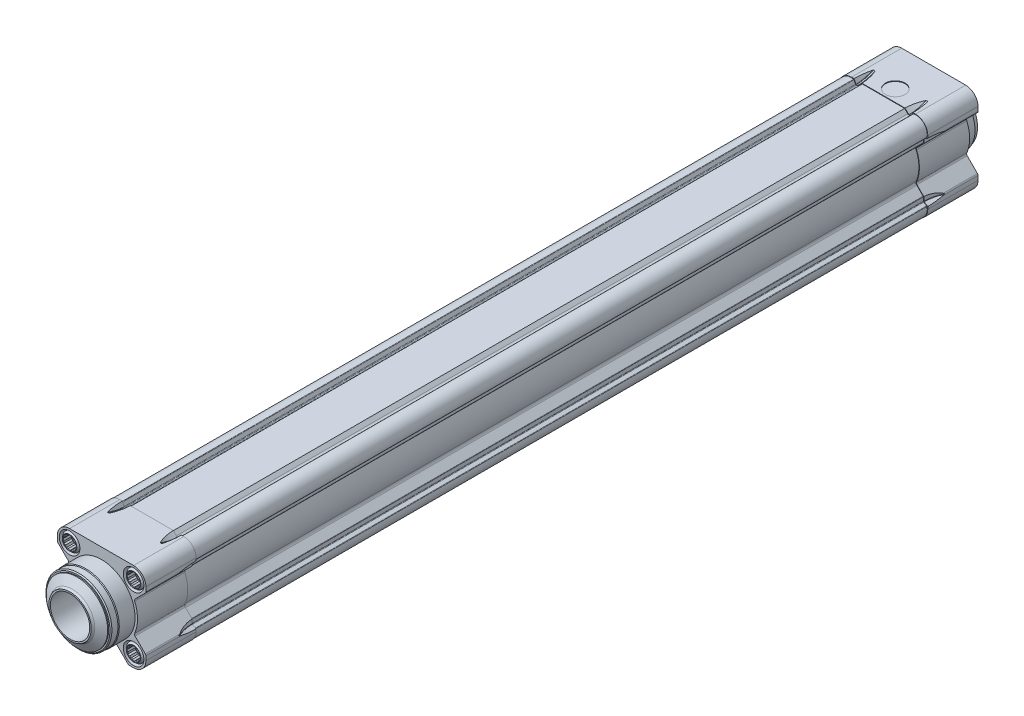
SolidWorks part; units mm, degrees
ref_plane "Front Plane" through (0, 0, 0) normal (0, 0, 1) x (1, 0, 0)
ref_plane "Top Plane" through (0, 0, 0) normal (0, 1, 0) x (1, 0, 0)
ref_plane "Right Plane" through (0, 0, 0) normal (1, 0, 0) x (0, 0, -1)
ref_plane "Plane4" through (0, 0, -25.5) normal (0, 0, 1) x (1, 0, 0)
sketch "Sketch1" plane through (0, 0, -25.5) normal (0, 0, 1) x (1, 0, 0)
  line L0 (-22.2071, 13.3683) -> (-17.0289, 8.1901)
  line L1 (-17.0289, -8.1901) -> (-22.2071, -13.3683)
  line L2 (-22.5, -14.0754) -> (-22.5, -16.25)
  line L3 (-16.25, -22.5) -> (-14.0754, -22.5)
  line L4 (-13.3683, -22.2071) -> (-8.1901, -17.0289)
  line L5 (8.1901, -17.0289) -> (13.3683, -22.2071)
  line L6 (14.0754, -22.5) -> (16.25, -22.5)
  line L7 (22.5, -16.25) -> (22.5, -14.0754)
  line L8 (22.2071, -13.3683) -> (17.0289, -8.1901)
  line L9 (17.0289, 8.1901) -> (22.2071, 13.3683)
  line L10 (22.5, 14.0754) -> (22.5, 16.25)
  line L11 (16.25, 22.5) -> (-16.25, 22.5)
  line L12 (-22.5, 16.25) -> (-22.5, 14.0754)
  arc A0 (-22.5, 14.0754) -> (-22.2071, 13.3683) centre (-21.5, 14.0754) ccw
  arc A1 (-17.0289, 8.1901) -> (-16.8147, 7.0943) centre (-17.736, 7.483) cw
  arc A2 (-16.8147, 7.0943) -> (-16.8147, -7.0943) centre (0, 0) ccw
  arc A3 (-16.8147, -7.0943) -> (-17.0289, -8.1901) centre (-17.736, -7.483) cw
  arc A4 (-22.2071, -13.3683) -> (-22.5, -14.0754) centre (-21.5, -14.0754) ccw
  arc A5 (-22.5, -16.25) -> (-16.25, -22.5) centre (-16.25, -16.25) ccw
  arc A6 (-14.0754, -22.5) -> (-13.3683, -22.2071) centre (-14.0754, -21.5) ccw
  arc A7 (-8.1901, -17.0289) -> (-7.0943, -16.8147) centre (-7.483, -17.736) cw
  arc A8 (-7.0943, -16.8147) -> (7.0943, -16.8147) centre (0, 0) ccw
  arc A9 (7.0943, -16.8147) -> (8.1901, -17.0289) centre (7.483, -17.736) cw
  arc A10 (13.3683, -22.2071) -> (14.0754, -22.5) centre (14.0754, -21.5) ccw
  arc A11 (16.25, -22.5) -> (22.5, -16.25) centre (16.25, -16.25) ccw
  arc A12 (22.5, -14.0754) -> (22.2071, -13.3683) centre (21.5, -14.0754) ccw
  arc A13 (17.0289, -8.1901) -> (16.8147, -7.0943) centre (17.736, -7.483) cw
  arc A14 (16.8147, -7.0943) -> (16.8147, 7.0943) centre (0, 0) ccw
  arc A15 (16.8147, 7.0943) -> (17.0289, 8.1901) centre (17.736, 7.483) cw
  arc A16 (22.2071, 13.3683) -> (22.5, 14.0754) centre (21.5, 14.0754) ccw
  arc A17 (22.5, 16.25) -> (16.25, 22.5) centre (16.25, 16.25) ccw
  arc A18 (-16.25, 22.5) -> (-22.5, 16.25) centre (-16.25, 16.25) ccw
extrude "Boss-Extrude1" add sketch "Sketch1" along normal blind 25.5
sketch "Sketch2" plane through (0, 0, -25.5) normal (0, 0, 1) x (1, 0, 0)
  line L0 (-15, 28.125) -> (-15, 22.5)
  line L1 (-15, 22.5) -> (-13.903, 20.6)
  line L2 (-13.7298, 20.5) -> (-13.0281, 20.5)
  line L3 (-12.8867, 20.5586) -> (-10.9453, 22.5)
  line L4 (-10.9453, 22.5) -> (10.9453, 22.5)
  line L5 (10.9453, 22.5) -> (12.8867, 20.5586)
  line L6 (13.0281, 20.5) -> (13.7298, 20.5)
  line L7 (13.903, 20.6) -> (15, 22.5)
  line L8 (15, 22.5) -> (15, 28.125)
  line L9 (15, 28.125) -> (-15, 28.125)
  line L10 (-50, 40.5) -> (50, 40.5) construction
  arc A0 (-13.903, 20.6) -> (-13.7298, 20.5) centre (-13.7298, 20.7) ccw
  arc A1 (-13.0281, 20.5) -> (-12.8867, 20.5586) centre (-13.0281, 20.7) ccw
  arc A2 (12.8867, 20.5586) -> (13.0281, 20.5) centre (13.0281, 20.7) ccw
  arc A3 (13.7298, 20.5) -> (13.903, 20.6) centre (13.7298, 20.7) ccw
revolve "Cut-Revolve1" cut sketch "Sketch2" angle 360 about L10 reverse direction yes
sketch "Sketch3" plane through (0, 0, -25.5) normal (0, 0, 1) x (1, 0, 0)
  line L0 (-15, -28.125) -> (15, -28.125)
  line L1 (15, -28.125) -> (15, -22.5)
  line L2 (15, -22.5) -> (13.903, -20.6)
  line L3 (13.7298, -20.5) -> (5.5958, -20.5)
  line L4 (-5.5958, -20.5) -> (-13.7298, -20.5)
  line L5 (-13.903, -20.6) -> (-15, -22.5)
  line L6 (-15, -22.5) -> (-15, -28.125)
  line L7 (50, -40.5) -> (-50, -40.5) construction
  arc A0 (13.903, -20.6) -> (13.7298, -20.5) centre (13.7298, -20.7) ccw
  arc A1 (5.5958, -20.5) -> (-5.5958, -20.5) centre (0, 0) cw
  arc A2 (-13.7298, -20.5) -> (-13.903, -20.6) centre (-13.7298, -20.7) ccw
revolve "Cut-Revolve2" cut sketch "Sketch3" angle 360 about L7 reverse direction yes
sketch "Sketch4" plane through (0, 0, -25.5) normal (0, 0, 1) x (1, 0, 0)
  line L0 (20.5, -5.5958) -> (20.5, -13.7298)
  line L1 (20.6, -13.903) -> (22.5, -15)
  line L2 (22.5, -15) -> (28.125, -15)
  line L3 (28.125, -15) -> (28.125, 15)
  line L4 (28.125, 15) -> (22.5, 15)
  line L5 (22.5, 15) -> (20.6, 13.903)
  line L6 (20.5, 13.7298) -> (20.5, 5.5958)
  line L7 (40.5, 50) -> (40.5, -50) construction
  arc A0 (20.5, -13.7298) -> (20.6, -13.903) centre (20.7, -13.7298) ccw
  arc A1 (20.6, 13.903) -> (20.5, 13.7298) centre (20.7, 13.7298) ccw
  arc A2 (20.5, 5.5958) -> (20.5, -5.5958) centre (0, 0) cw
revolve "Cut-Revolve3" cut sketch "Sketch4" angle 360 about L7 reverse direction yes
sketch "Sketch5" plane through (0, 0, -25.5) normal (0, 0, 1) x (1, 0, 0)
  line L0 (-28.125, -15) -> (-22.5, -15)
  line L1 (-22.5, -15) -> (-20.6, -13.903)
  line L2 (-20.5, -13.7298) -> (-20.5, -5.5958)
  line L3 (-20.5, 5.5958) -> (-20.5, 13.7298)
  line L4 (-20.6, 13.903) -> (-22.5, 15)
  line L5 (-22.5, 15) -> (-28.125, 15)
  line L6 (-28.125, 15) -> (-28.125, -15)
  line L7 (-40.5, -50) -> (-40.5, 50) construction
  arc A0 (-20.6, -13.903) -> (-20.5, -13.7298) centre (-20.7, -13.7298) ccw
  arc A1 (-20.5, -5.5958) -> (-20.5, 5.5958) centre (0, 0) cw
  arc A2 (-20.5, 13.7298) -> (-20.6, 13.903) centre (-20.7, 13.7298) ccw
revolve "Cut-Revolve4" cut sketch "Sketch5" angle 360 about L7 reverse direction yes
sketch "Sketch6" plane through (0, 0, 0) normal (1, 0, 0) x (0, 0, -1)
  line L0 (25.5, 0) -> (25.5, 5)
  line L1 (25.5, 5) -> (397, 5)
  line L2 (397, 5) -> (397, 0)
  line L3 (397, 0) -> (25.5, 0)
  line L4 (397, 0) -> (25.5, 0) construction
revolve "Revolve1" add sketch "Sketch6" angle 360 about L4 reverse direction yes
ref_plane "Plane5" through (0, 0, -397) normal (0, 0, 1) x (1, 0, 0)
sketch "Sketch7" plane through (0, 0, -397) normal (0, 0, 1) x (1, 0, 0)
  line L0 (-22.2071, 13.3683) -> (-17.0289, 8.1901)
  line L1 (-17.0289, -8.1901) -> (-22.2071, -13.3683)
  line L2 (-22.5, -14.0754) -> (-22.5, -16.25)
  line L3 (-16.25, -22.5) -> (-14.0754, -22.5)
  line L4 (-13.3683, -22.2071) -> (-8.1901, -17.0289)
  line L5 (8.1901, -17.0289) -> (13.3683, -22.2071)
  line L6 (14.0754, -22.5) -> (16.25, -22.5)
  line L7 (22.5, -16.25) -> (22.5, -14.0754)
  line L8 (22.2071, -13.3683) -> (17.0289, -8.1901)
  line L9 (17.0289, 8.1901) -> (22.2071, 13.3683)
  line L10 (22.5, 14.0754) -> (22.5, 16.25)
  line L11 (16.25, 22.5) -> (-16.25, 22.5)
  line L12 (-22.5, 16.25) -> (-22.5, 14.0754)
  arc A0 (-22.5, 14.0754) -> (-22.2071, 13.3683) centre (-21.5, 14.0754) ccw
  arc A1 (-17.0289, 8.1901) -> (-16.8147, 7.0943) centre (-17.736, 7.483) cw
  arc A2 (-16.8147, 7.0943) -> (-16.8147, -7.0943) centre (0, 0) ccw
  arc A3 (-16.8147, -7.0943) -> (-17.0289, -8.1901) centre (-17.736, -7.483) cw
  arc A4 (-22.2071, -13.3683) -> (-22.5, -14.0754) centre (-21.5, -14.0754) ccw
  arc A5 (-22.5, -16.25) -> (-16.25, -22.5) centre (-16.25, -16.25) ccw
  arc A6 (-14.0754, -22.5) -> (-13.3683, -22.2071) centre (-14.0754, -21.5) ccw
  arc A7 (-8.1901, -17.0289) -> (-7.0943, -16.8147) centre (-7.483, -17.736) cw
  arc A8 (-7.0943, -16.8147) -> (7.0943, -16.8147) centre (0, 0) ccw
  arc A9 (7.0943, -16.8147) -> (8.1901, -17.0289) centre (7.483, -17.736) cw
  arc A10 (13.3683, -22.2071) -> (14.0754, -22.5) centre (14.0754, -21.5) ccw
  arc A11 (16.25, -22.5) -> (22.5, -16.25) centre (16.25, -16.25) ccw
  arc A12 (22.5, -14.0754) -> (22.2071, -13.3683) centre (21.5, -14.0754) ccw
  arc A13 (17.0289, -8.1901) -> (16.8147, -7.0943) centre (17.736, -7.483) cw
  arc A14 (16.8147, -7.0943) -> (16.8147, 7.0943) centre (0, 0) ccw
  arc A15 (16.8147, 7.0943) -> (17.0289, 8.1901) centre (17.736, 7.483) cw
  arc A16 (22.2071, 13.3683) -> (22.5, 14.0754) centre (21.5, 14.0754) ccw
  arc A17 (22.5, 16.25) -> (16.25, 22.5) centre (16.25, 16.25) ccw
  arc A18 (-16.25, 22.5) -> (-22.5, 16.25) centre (-16.25, 16.25) ccw
extrude "Boss-Extrude2" add sketch "Sketch7" against normal blind 25.5
sketch "Sketch8" plane through (0, 0, -397) normal (0, 0, 1) x (1, 0, 0)
  line L0 (-15, 28.125) -> (-15, 22.5)
  line L1 (-15, 22.5) -> (-13.903, 20.6)
  line L2 (-13.7298, 20.5) -> (-13.0281, 20.5)
  line L3 (-12.8867, 20.5586) -> (-10.9453, 22.5)
  line L4 (-10.9453, 22.5) -> (10.9453, 22.5)
  line L5 (10.9453, 22.5) -> (12.8867, 20.5586)
  line L6 (13.0281, 20.5) -> (13.7298, 20.5)
  line L7 (13.903, 20.6) -> (15, 22.5)
  line L8 (15, 22.5) -> (15, 28.125)
  line L9 (15, 28.125) -> (-15, 28.125)
  line L10 (-50, 40.5) -> (50, 40.5) construction
  arc A0 (-13.903, 20.6) -> (-13.7298, 20.5) centre (-13.7298, 20.7) ccw
  arc A1 (-13.0281, 20.5) -> (-12.8867, 20.5586) centre (-13.0281, 20.7) ccw
  arc A2 (12.8867, 20.5586) -> (13.0281, 20.5) centre (13.0281, 20.7) ccw
  arc A3 (13.7298, 20.5) -> (13.903, 20.6) centre (13.7298, 20.7) ccw
revolve "Cut-Revolve5" cut sketch "Sketch8" angle 360 about L10 reverse direction yes
sketch "Sketch9" plane through (0, 0, -397) normal (0, 0, 1) x (1, 0, 0)
  line L0 (-15, -30) -> (15, -30)
  line L1 (15, -30) -> (15, -22.5)
  line L2 (15, -22.5) -> (13.903, -20.6)
  line L3 (13.7298, -20.5) -> (5.5958, -20.5)
  line L4 (-5.5958, -20.5) -> (-13.7298, -20.5)
  line L5 (-13.903, -20.6) -> (-15, -22.5)
  line L6 (-15, -22.5) -> (-15, -30)
  line L7 (50, -40.5) -> (-50, -40.5) construction
  arc A0 (13.903, -20.6) -> (13.7298, -20.5) centre (13.7298, -20.7) ccw
  arc A1 (5.5958, -20.5) -> (-5.5958, -20.5) centre (0, 0) cw
  arc A2 (-13.7298, -20.5) -> (-13.903, -20.6) centre (-13.7298, -20.7) ccw
revolve "Cut-Revolve6" cut sketch "Sketch9" angle 360 about L7 reverse direction yes
sketch "Sketch10" plane through (0, 0, -397) normal (0, 0, 1) x (1, 0, 0)
  line L0 (20.5, -5.5958) -> (20.5, -13.7298)
  line L1 (20.6, -13.903) -> (22.5, -15)
  line L2 (22.5, -15) -> (28.125, -15)
  line L3 (28.125, -15) -> (28.125, 15)
  line L4 (28.125, 15) -> (22.5, 15)
  line L5 (22.5, 15) -> (20.6, 13.903)
  line L6 (20.5, 13.7298) -> (20.5, 5.5958)
  line L7 (40.5, 50) -> (40.5, -50) construction
  arc A0 (20.5, -13.7298) -> (20.6, -13.903) centre (20.7, -13.7298) ccw
  arc A1 (20.6, 13.903) -> (20.5, 13.7298) centre (20.7, 13.7298) ccw
  arc A2 (20.5, 5.5958) -> (20.5, -5.5958) centre (0, 0) cw
revolve "Cut-Revolve7" cut sketch "Sketch10" angle 360 about L7 reverse direction yes
sketch "Sketch11" plane through (0, 0, -397) normal (0, 0, 1) x (1, 0, 0)
  line L0 (-28.125, -15) -> (-22.5, -15)
  line L1 (-22.5, -15) -> (-20.6, -13.903)
  line L2 (-20.5, -13.7298) -> (-20.5, -5.5958)
  line L3 (-20.5, 5.5958) -> (-20.5, 13.7298)
  line L4 (-20.6, 13.903) -> (-22.5, 15)
  line L5 (-22.5, 15) -> (-28.125, 15)
  line L6 (-28.125, 15) -> (-28.125, -15)
  line L7 (-40.5, -50) -> (-40.5, 50) construction
  arc A0 (-20.6, -13.903) -> (-20.5, -13.7298) centre (-20.7, -13.7298) ccw
  arc A1 (-20.5, -5.5958) -> (-20.5, 5.5958) centre (0, 0) cw
  arc A2 (-20.5, 13.7298) -> (-20.6, 13.903) centre (-20.7, 13.7298) ccw
revolve "Cut-Revolve8" cut sketch "Sketch11" angle 360 about L7 reverse direction yes
sketch "Sketch12" plane through (0, 0, -25.5) normal (0, 0, 1) x (1, 0, 0)
  line L0 (-14.9895, -21.9218) -> (-14.1397, -20.45)
  line L1 (-13.7933, -20.25) -> (-11.9304, -20.25)
  line L2 (-11.6476, -20.1328) -> (-8.4853, -16.9706)
  line L3 (8.4853, -16.9706) -> (11.6476, -20.1328)
  line L4 (11.9304, -20.25) -> (13.7933, -20.25)
  line L5 (14.1397, -20.45) -> (14.9895, -21.9218)
  line L6 (21.9218, -14.9895) -> (20.45, -14.1397)
  line L7 (20.25, -13.7933) -> (20.25, -11.9304)
  line L8 (20.1328, -11.6476) -> (16.9706, -8.4853)
  line L9 (16.2426, 7.7574) -> (20.1328, 11.6476)
  line L10 (20.25, 11.9304) -> (20.25, 13.7933)
  line L11 (20.45, 14.1397) -> (21.9218, 14.9895)
  line L12 (14.9895, 21.9218) -> (14.1397, 20.45)
  line L13 (13.7933, 20.25) -> (13.3713, 20.25)
  line L14 (12.3107, 20.6893) -> (10.75, 22.25)
  line L15 (10.75, 22.25) -> (-10.75, 22.25)
  line L16 (-10.75, 22.25) -> (-12.3107, 20.6893)
  line L17 (-13.3713, 20.25) -> (-13.7933, 20.25)
  line L18 (-14.1397, 20.45) -> (-14.9895, 21.9218)
  line L19 (-21.9218, 14.9895) -> (-20.45, 14.1397)
  line L20 (-20.25, 13.7933) -> (-20.25, 11.9304)
  line L21 (-20.1328, 11.6476) -> (-16.2426, 7.7574)
  line L22 (-16.9706, -8.4853) -> (-20.1328, -11.6476)
  line L23 (-20.25, -11.9304) -> (-20.25, -13.7933)
  line L24 (-20.45, -14.1397) -> (-21.9218, -14.9895)
  arc A0 (-22.1122, -15.2488) -> (-15.2488, -22.1122) centre (-16.5, -16.5) ccw
  arc A1 (-15.2488, -22.1122) -> (-14.9895, -21.9218) centre (-15.3359, -21.7218) ccw
  arc A2 (-14.1397, -20.45) -> (-13.7933, -20.25) centre (-13.7933, -20.65) cw
  arc A3 (-11.9304, -20.25) -> (-11.6476, -20.1328) centre (-11.9304, -19.85) ccw
  arc A4 (-8.4853, -16.9706) -> (-6.8535, -16.6442) centre (-7.4246, -18.0312) cw
  arc A5 (-6.8535, -16.6442) -> (6.8535, -16.6442) centre (0, 0) ccw
  arc A6 (6.8535, -16.6442) -> (8.4853, -16.9706) centre (7.4246, -18.0312) cw
  arc A7 (11.6476, -20.1328) -> (11.9304, -20.25) centre (11.9304, -19.85) ccw
  arc A8 (13.7933, -20.25) -> (14.1397, -20.45) centre (13.7933, -20.65) cw
  arc A9 (14.9895, -21.9218) -> (15.2488, -22.1122) centre (15.3359, -21.7218) ccw
  arc A10 (15.2488, -22.1122) -> (22.1122, -15.2488) centre (16.5, -16.5) ccw
  arc A11 (22.1122, -15.2488) -> (21.9218, -14.9895) centre (21.7218, -15.3359) ccw
  arc A12 (20.45, -14.1397) -> (20.25, -13.7933) centre (20.65, -13.7933) cw
  arc A13 (20.25, -11.9304) -> (20.1328, -11.6476) centre (19.85, -11.9304) ccw
  arc A14 (16.9706, -8.4853) -> (16.6442, -6.8535) centre (18.0312, -7.4246) cw
  arc A15 (16.6442, -6.8535) -> (16.2426, 7.7574) centre (0, 0) ccw
  arc A16 (20.1328, 11.6476) -> (20.25, 11.9304) centre (19.85, 11.9304) ccw
  arc A17 (20.25, 13.7933) -> (20.45, 14.1397) centre (20.65, 13.7933) cw
  arc A18 (21.9218, 14.9895) -> (22.1122, 15.2488) centre (21.7218, 15.3359) ccw
  arc A19 (22.1122, 15.2488) -> (15.2488, 22.1122) centre (16.5, 16.5) ccw
  arc A20 (15.2488, 22.1122) -> (14.9895, 21.9218) centre (15.3359, 21.7218) ccw
  arc A21 (14.1397, 20.45) -> (13.7933, 20.25) centre (13.7933, 20.65) cw
  arc A22 (13.3713, 20.25) -> (12.3107, 20.6893) centre (13.3713, 21.75) cw
  arc A23 (-12.3107, 20.6893) -> (-13.3713, 20.25) centre (-13.3713, 21.75) cw
  arc A24 (-13.7933, 20.25) -> (-14.1397, 20.45) centre (-13.7933, 20.65) cw
  arc A25 (-14.9895, 21.9218) -> (-15.2488, 22.1122) centre (-15.3359, 21.7218) ccw
  arc A26 (-15.2488, 22.1122) -> (-22.1122, 15.2488) centre (-16.5, 16.5) ccw
  arc A27 (-22.1122, 15.2488) -> (-21.9218, 14.9895) centre (-21.7218, 15.3359) ccw
  arc A28 (-20.45, 14.1397) -> (-20.25, 13.7933) centre (-20.65, 13.7933) cw
  arc A29 (-20.25, 11.9304) -> (-20.1328, 11.6476) centre (-19.85, 11.9304) ccw
  arc A30 (-16.2426, 7.7574) -> (-16.6442, -6.8535) centre (0, 0) ccw
  arc A31 (-16.6442, -6.8535) -> (-16.9706, -8.4853) centre (-18.0312, -7.4246) cw
  arc A32 (-20.1328, -11.6476) -> (-20.25, -11.9304) centre (-19.85, -11.9304) ccw
  arc A33 (-20.25, -13.7933) -> (-20.45, -14.1397) centre (-20.65, -13.7933) cw
  arc A34 (-21.9218, -14.9895) -> (-22.1122, -15.2488) centre (-21.7218, -15.3359) ccw
extrude "Boss-Extrude3" add sketch "Sketch12" against normal blind 371.5
sketch "Sketch13" plane through (0, 0, 0) normal (1, 0, 0) x (0, 0, -1)
  line L0 (-16, 0) -> (-16, 10.75)
  line L1 (-14.8683, 11.4103) -> (-12.5, 15.6)
  line L2 (-12.5, 15.6) -> (-12, 15.6)
  line L3 (-12, 15.6) -> (-12, 16.25)
  line L4 (-12, 16.25) -> (-11.5, 16.75)
  line L5 (-11.5, 16.75) -> (-8.433, 16.75)
  line L6 (-8.433, 16.75) -> (-8, 17)
  line L7 (-8, 17) -> (0, 17)
  line L8 (0, 17) -> (0, 0)
  line L9 (0, 0) -> (-16, 0)
  line L10 (0, 0) -> (-16, 0) construction
  arc A0 (-16, 10.75) -> (-14.8683, 11.4103) centre (-16, 12.05) ccw
revolve "Revolve2" add sketch "Sketch13" angle 360 about L10 reverse direction yes
ref_plane "Plane6" through (0, 0, -403) normal (0, 0, 1) x (1, 0, 0)
sketch "Sketch14" plane through (0, 0, -403) normal (0, 0, 1) x (1, 0, 0)
  line L0 (0, 22.5) -> (5, 22.5)
  line L1 (5, 22.5) -> (5, 22.2)
  line L2 (5, 22.2) -> (0, 22.2)
  line L3 (0, 22.2) -> (0, 22.5)
  line L4 (0, 22.2) -> (0, 22.5) construction
revolve "Cut-Revolve9" cut sketch "Sketch14" angle 360 about L4 reverse direction yes
ref_plane "Plane7" through (0, 22.5, 0) normal (0, 1, 0) x (1, 0, 0)
ref_plane "Plane8" through (16.25, 0, 0) normal (1, 0, 0) x (0, 0, -1)
sketch "Sketch15" plane through (16.25, 0, 0) normal (1, 0, 0) x (0, 0, -1)
  line L0 (0, 16.25) -> (0, 21.5)
  line L1 (0, 21.5) -> (21.1, 21.5)
  line L2 (21.1, 21.5) -> (21.1, 16.25)
  line L3 (21.1, 16.25) -> (0, 16.25)
  line L4 (21.1, 16.25) -> (0, 16.25) construction
revolve "Cut-Revolve10" cut sketch "Sketch15" angle 360 about L4 reverse direction yes
sketch "Sketch16" plane through (0, 0, 0) normal (0, 0, 1) x (1, 0, 0)
  line L0 (16.25, 16.25) -> (-16.25, 16.25)
  line L1 (16.25, 16.25) -> (16.25, -16.25)
pattern_linear "LPattern1" count 2 spacing 32.5 along (-1, 0, 0) count 2 spacing 32.5 along (0, -1, 0) of "Cut-Revolve10"
sketch "Sketch17" plane through (16.25, 0, 0) normal (1, 0, 0) x (0, 0, -1)
  line L0 (0, 16.25) -> (0, 19.9109)
  line L1 (0, 19.9109) -> (1, 20.75)
  line L2 (1, 20.75) -> (21.1, 20.75)
  line L3 (21.1, 20.75) -> (21.1, 16.25)
  line L4 (21.1, 16.25) -> (0, 16.25)
  line L5 (21.1, 16.25) -> (0, 16.25) construction
revolve "Revolve3" add sketch "Sketch17" angle 360 about L5 reverse direction yes
sketch "Sketch18" plane through (0, 0, 0) normal (0, 0, 1) x (1, 0, 0)
  line L0 (16.25, 16.25) -> (-16.25, 16.25)
  line L1 (16.25, 16.25) -> (16.25, -16.25)
pattern_linear "LPattern2" count 2 spacing 32.5 along (-1, 0, 0) count 2 spacing 32.5 along (0, -1, 0) of "Revolve3"
sketch "Sketch19" plane through (16.25, 0, 0) normal (1, 0, 0) x (0, 0, -1)
  line L0 (0, 16.25) -> (0, 19.75)
  line L1 (0, 19.75) -> (0.2887, 19.25)
  line L2 (0.2887, 19.25) -> (5.5, 19.25)
  line L3 (5.5, 19.25) -> (6.0415, 18.7085)
  line L4 (6.0415, 18.7085) -> (18.7, 18.7085)
  line L5 (18.7, 18.7085) -> (20.1194, 16.25)
  line L6 (20.1194, 16.25) -> (0, 16.25)
  line L7 (20.1194, 16.25) -> (0, 16.25) construction
revolve "Cut-Revolve11" cut sketch "Sketch19" angle 360 about L7 reverse direction yes
cosmetic thread "Cosmetic Thread1" parameters "D1"=10.5, "D2"=6
sketch "Sketch20" plane through (0, 0, 0) normal (0, 0, 1) x (1, 0, 0)
  line L0 (12.7859, 16.25) -> (13.25, 15.4462)
  line L1 (13.25, 15.4462) -> (13.25, 14.5179)
  line L2 (13.25, 14.5179) -> (14.0538, 14.0538)
  line L3 (14.0538, 14.0538) -> (14.5179, 13.25)
  line L4 (14.5179, 13.25) -> (15.4462, 13.25)
  line L5 (15.4462, 13.25) -> (16.25, 12.7859)
  line L6 (16.25, 12.7859) -> (17.0538, 13.25)
  line L7 (17.0538, 13.25) -> (17.9821, 13.25)
  line L8 (17.9821, 13.25) -> (18.4462, 14.0538)
  line L9 (18.4462, 14.0538) -> (19.25, 14.5179)
  line L10 (19.25, 14.5179) -> (19.25, 15.4462)
  line L11 (19.25, 15.4462) -> (19.7141, 16.25)
  line L12 (19.7141, 16.25) -> (19.25, 17.0538)
  line L13 (19.25, 17.0538) -> (19.25, 17.9821)
  line L14 (19.25, 17.9821) -> (18.4462, 18.4462)
  line L15 (18.4462, 18.4462) -> (17.9821, 19.25)
  line L16 (17.9821, 19.25) -> (17.0538, 19.25)
  line L17 (17.0538, 19.25) -> (16.25, 19.7141)
  line L18 (16.25, 19.7141) -> (15.4462, 19.25)
  line L19 (15.4462, 19.25) -> (14.5179, 19.25)
  line L20 (14.5179, 19.25) -> (14.0538, 18.4462)
  line L21 (14.0538, 18.4462) -> (13.25, 17.9821)
  line L22 (13.25, 17.9821) -> (13.25, 17.0538)
  line L23 (13.25, 17.0538) -> (12.7859, 16.25)
extrude "Cut-Extrude1" cut sketch "Sketch20" along normal blind 4 and the other way blind 4
sketch "Sketch21" plane through (0, 0, 0) normal (0, 0, 1) x (1, 0, 0)
  line L0 (16.25, 16.25) -> (-16.25, 16.25)
  line L1 (16.25, 16.25) -> (16.25, -16.25)
pattern_linear "LPattern3" count 2 spacing 32.5 along (-1, 0, 0) count 2 spacing 32.5 along (0, -1, 0) of "Cut-Revolve11"
sketch "Sketch22" plane through (0, 0, 0) normal (0, 0, 1) x (1, 0, 0)
  line L0 (16.25, 16.25) -> (-16.25, 16.25)
  line L1 (16.25, 16.25) -> (16.25, -16.25)
pattern_linear "LPattern4" count 2 spacing 32.5 along (-1, 0, 0) count 2 spacing 32.5 along (0, -1, 0) of "Cut-Extrude1"
ref_plane "Plane9" through (0, 0, -422.5) normal (0, 0, 1) x (1, 0, 0)
sketch "Sketch23" plane through (0, 0, 0) normal (1, 0, 0) x (0, 0, -1)
  line L0 (422.5, 0) -> (422.5, 16)
  line L1 (422.5, 16) -> (427.5, 16)
  line L2 (427.5, 16) -> (429.5, 15.2721)
  line L3 (429.5, 15.2721) -> (429.5, 0)
  line L4 (429.5, 0) -> (422.5, 0)
  line L5 (429.5, 0) -> (422.5, 0) construction
revolve "Revolve4" add sketch "Sketch23" angle 360 about L5 reverse direction yes
sketch "Sketch24" plane through (0, 0, 0) normal (1, 0, 0) x (0, 0, -1)
  line L0 (397, 0) -> (397, 4)
  line L1 (397, 4) -> (424.24, 4)
  line L2 (424.24, 4) -> (424.24, 12)
  line L3 (424.24, 12) -> (428.5, 12)
  line L4 (428.5, 12) -> (429.5, 12.364)
  line L5 (429.5, 12.364) -> (429.5, 0)
  line L6 (429.5, 0) -> (397, 0)
  line L7 (429.5, 0) -> (397, 0) construction
revolve "Cut-Revolve12" cut sketch "Sketch24" angle 360 about L7 reverse direction yes
ref_plane "Plane10" through (0, 0, 0) normal (1, 0, 0) x (0, 0, -1)
sketch "Sketch25" plane through (16.25, 0, 0) normal (1, 0, 0) x (0, 0, -1)
  line L0 (401.4, 16.25) -> (401.4, 21.5)
  line L1 (401.4, 21.5) -> (422.5, 21.5)
  line L2 (422.5, 21.5) -> (422.5, 16.25)
  line L3 (422.5, 16.25) -> (401.4, 16.25)
  line L4 (422.5, 16.25) -> (401.4, 16.25) construction
revolve "Cut-Revolve13" cut sketch "Sketch25" angle 360 about L4 reverse direction yes
sketch "Sketch26" plane through (0, 0, -422.5) normal (0, 0, 1) x (1, 0, 0)
  line L0 (16.25, 16.25) -> (-16.25, 16.25)
  line L1 (16.25, 16.25) -> (16.25, -16.25)
pattern_linear "LPattern5" count 2 spacing 32.5 along (-1, 0, 0) count 2 spacing 32.5 along (0, -1, 0) of "Cut-Revolve13"
sketch "Sketch27" plane through (16.25, 0, 0) normal (1, 0, 0) x (0, 0, -1)
  line L0 (401.4, 16.25) -> (401.4, 20.75)
  line L1 (401.4, 20.75) -> (421.5, 20.75)
  line L2 (421.5, 20.75) -> (422.5, 19.9109)
  line L3 (422.5, 19.9109) -> (422.5, 16.25)
  line L4 (422.5, 16.25) -> (401.4, 16.25)
  line L5 (422.5, 16.25) -> (401.4, 16.25) construction
revolve "Revolve5" add sketch "Sketch27" angle 360 about L5 reverse direction yes
sketch "Sketch28" plane through (0, 0, -422.5) normal (0, 0, 1) x (1, 0, 0)
  line L0 (16.25, 16.25) -> (-16.25, 16.25)
  line L1 (16.25, 16.25) -> (16.25, -16.25)
pattern_linear "LPattern6" count 2 spacing 32.5 along (-1, 0, 0) count 2 spacing 32.5 along (0, -1, 0) of "Revolve5"
sketch "Sketch29" plane through (16.25, 0, 0) normal (1, 0, 0) x (0, 0, -1)
  line L0 (402.3806, 16.25) -> (403.8, 18.7085)
  line L1 (403.8, 18.7085) -> (416.4585, 18.7085)
  line L2 (416.4585, 18.7085) -> (417, 19.25)
  line L3 (417, 19.25) -> (422.2113, 19.25)
  line L4 (422.2113, 19.25) -> (422.5, 19.75)
  line L5 (422.5, 19.75) -> (422.5, 16.25)
  line L6 (422.5, 16.25) -> (402.3806, 16.25)
  line L7 (422.5, 16.25) -> (402.3806, 16.25) construction
revolve "Cut-Revolve14" cut sketch "Sketch29" angle 360 about L7 reverse direction yes
cosmetic thread "Cosmetic Thread2" parameters "D1"=10.5, "D2"=6
sketch "Sketch30" plane through (0, 0, -422.5) normal (0, 0, 1) x (1, 0, 0)
  line L0 (16.25, 16.25) -> (-16.25, 16.25)
  line L1 (16.25, 16.25) -> (16.25, -16.25)
pattern_linear "LPattern7" count 2 spacing 32.5 along (-1, 0, 0) count 2 spacing 32.5 along (0, -1, 0) of "Cut-Revolve14"
sketch "Sketch31" plane through (0, 0, -422.5) normal (0, 0, 1) x (1, 0, 0)
  line L0 (12.7859, 16.25) -> (13.25, 15.4462)
  line L1 (13.25, 15.4462) -> (13.25, 14.5179)
  line L2 (13.25, 14.5179) -> (14.0538, 14.0538)
  line L3 (14.0538, 14.0538) -> (14.5179, 13.25)
  line L4 (14.5179, 13.25) -> (15.4462, 13.25)
  line L5 (15.4462, 13.25) -> (16.25, 12.7859)
  line L6 (16.25, 12.7859) -> (17.0538, 13.25)
  line L7 (17.0538, 13.25) -> (17.9821, 13.25)
  line L8 (17.9821, 13.25) -> (18.4462, 14.0538)
  line L9 (18.4462, 14.0538) -> (19.25, 14.5179)
  line L10 (19.25, 14.5179) -> (19.25, 15.4462)
  line L11 (19.25, 15.4462) -> (19.7141, 16.25)
  line L12 (19.7141, 16.25) -> (19.25, 17.0538)
  line L13 (19.25, 17.0538) -> (19.25, 17.9821)
  line L14 (19.25, 17.9821) -> (18.4462, 18.4462)
  line L15 (18.4462, 18.4462) -> (17.9821, 19.25)
  line L16 (17.9821, 19.25) -> (17.0538, 19.25)
  line L17 (17.0538, 19.25) -> (16.25, 19.7141)
  line L18 (16.25, 19.7141) -> (15.4462, 19.25)
  line L19 (15.4462, 19.25) -> (14.5179, 19.25)
  line L20 (14.5179, 19.25) -> (14.0538, 18.4462)
  line L21 (14.0538, 18.4462) -> (13.25, 17.9821)
  line L22 (13.25, 17.9821) -> (13.25, 17.0538)
  line L23 (13.25, 17.0538) -> (12.7859, 16.25)
extrude "Cut-Extrude2" cut sketch "Sketch31" along normal blind 4 and the other way blind 4
sketch "Sketch32" plane through (0, 0, -422.5) normal (0, 0, 1) x (1, 0, 0)
  line L0 (16.25, 16.25) -> (-16.25, 16.25)
  line L1 (16.25, 16.25) -> (16.25, -16.25)
pattern_linear "LPattern8" count 2 spacing 32.5 along (-1, 0, 0) count 2 spacing 32.5 along (0, -1, 0) of "Cut-Extrude2"
ref_plane "Plane11" through (0, 0, -397) normal (0, 0, 1) x (1, 0, 0)
sketch "Sketch33" plane through (0, 0, 0) normal (1, 0, 0) x (0, 0, -1)
  line L0 (-16, 0) -> (-16, 10)
  line L1 (-16, 10) -> (86.3333, 10)
  line L2 (86.3333, 10) -> (86.3333, 16)
  line L3 (86.3333, 16) -> (397, 16)
  line L4 (397, 16) -> (397, 0)
  line L5 (397, 0) -> (-16, 0)
  line L6 (397, 0) -> (-16, 0) construction
revolve "Cut-Revolve15" cut sketch "Sketch33" angle 360 about L6 reverse direction yes
ref_plane "Plane12" through (0, 0, -211.25) normal (0, 0, 1) x (1, 0, 0)
ref_plane "GUA XY" through (0, 0, -424.24) normal (0, 0, 1) x (1, 0, 0)
ref_plane "GUA XZ" through (0, 0, 0) normal (1, 0, 0) x (0, 0, -1)
ref_plane "GUA YZ" through (0, 0, 0) normal (0, 1, 0) x (1, 0, 0)
ref_axis "GUA X" through (0, -50, -424.24) along (0, 1, 0)
ref_axis "GUA Y" through (80.9, 0, -424.24) along (-1, 0, 0)
ref_axis "GUA Z" through (0, 0, 50) along (0, 0, -1)
sketch3d "GUA"
  point P0 (0, 0, -424.24)
ref_plane "KS XY" through (0, 0, -397) normal (0, 0, 1) x (1, 0, 0)
ref_plane "KS XZ" through (0, 0, 0) normal (0, -1, 0) x (-1, 0, 0)
ref_plane "KS YZ" through (0, 0, 0) normal (1, 0, 0) x (0, 0, -1)
ref_axis "KS X" through (-80.9, 0, -397) along (1, 0, 0)
ref_axis "KS Y" through (0, -50, -397) along (0, 1, 0)
ref_axis "KS Z" through (0, 0, 80.9) along (0, 0, -1)
sketch3d "KS"
  point P0 (0, 0, -397)
ref_plane "KSA XY" through (0, 0, -397) normal (0, 0, -1) x (-1, 0, 0)
ref_plane "KSA XZ" through (0, 0, 0) normal (0, 1, 0) x (1, 0, 0)
ref_plane "KSA YZ" through (0, 0, 0) normal (1, 0, 0) x (0, 0, -1)
ref_axis "KSA X" through (-80.9, 0, -397) along (1, 0, 0)
ref_axis "KSA Y" through (0, 50, -397) along (0, -1, 0)
ref_axis "KSA Z" through (0, 0, -80.9) along (0, 0, 1)
sketch3d "KSA"
  point P0 (0, 0, -397)
ref_plane "PLUG XY" through (0, 22.5, 0) normal (0, -1, 0) x (-1, 0, 0)
ref_plane "PLUG XZ" through (0, 0, -403) normal (0, 0, -1) x (-1, 0, 0)
ref_plane "PLUG YZ" through (0, 0, 0) normal (1, 0, 0) x (0, 0, -1)
ref_axis "PLUG X" through (-80.9, 22.5, -403) along (1, 0, 0)
ref_axis "PLUG Y" through (0, 22.5, -50) along (0, 0, 1)
ref_axis "PLUG Z" through (0, -50, -403) along (0, 1, 0)
sketch3d "PLUG"
  point P0 (0, 22.5, -403)
ref_plane "SENSOR XY" through (0, 0, -211.25) normal (0, 0, 1) x (1, 0, 0)
ref_plane "SENSOR XZ" through (0, 22.5, 0) normal (0, -1, 0) x (-1, 0, 0)
ref_plane "SENSOR YZ" through (0, 0, 0) normal (1, 0, 0) x (0, 0, -1)
ref_axis "SENSOR X" through (-80.9, 22.5, -211.25) along (1, 0, 0)
ref_axis "SENSOR Y" through (0, -50, -211.25) along (0, 1, 0)
ref_axis "SENSOR Z" through (0, 22.5, 80.9) along (0, 0, -1)
sketch3d "SENSOR"
  point P0 (0, 22.5, -211.25)
ref_plane "START XY" through (0, 0, 0) normal (0, 0, -1) x (-1, 0, 0)
ref_plane "START XZ" through (0, 0, 0) normal (0, 1, 0) x (1, 0, 0)
ref_plane "START YZ" through (0, 0, 0) normal (1, 0, 0) x (0, 0, -1)
ref_axis "START X" through (-80.9, 0, 0) along (1, 0, 0)
ref_axis "START Y" through (0, 50, 0) along (0, -1, 0)
ref_axis "START Z" through (0, 0, -80.9) along (0, 0, 1)
sketch3d "START"
  point P0 (0, 0, 0)
other "Freeze***"
